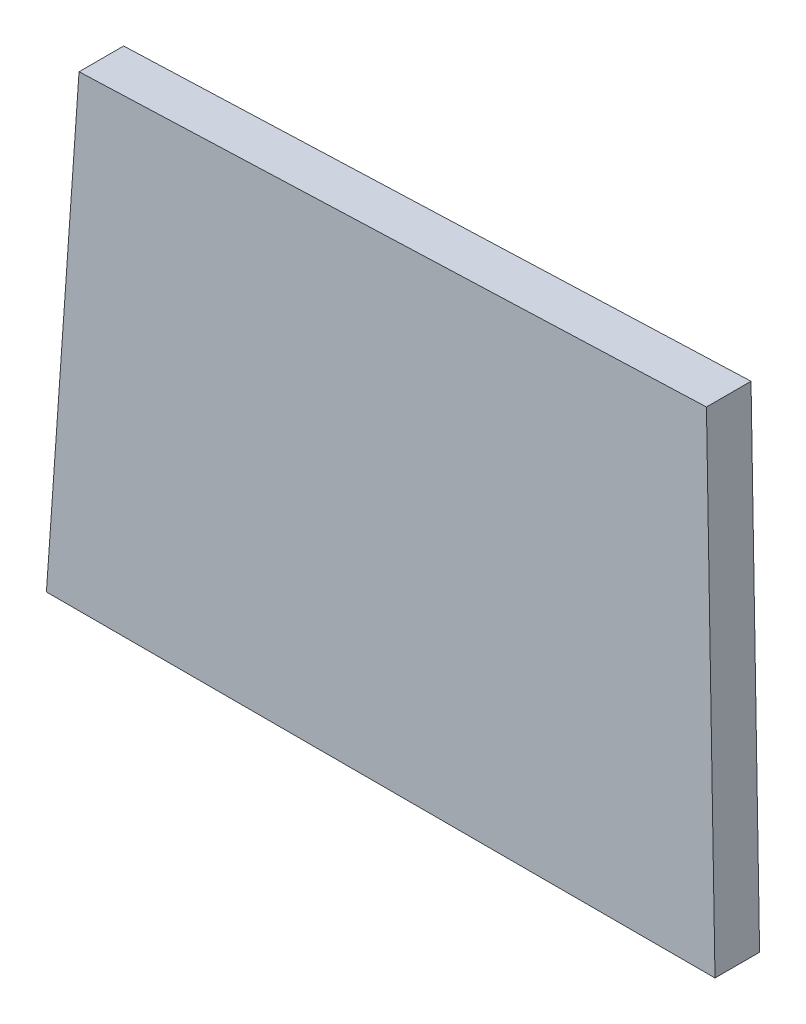
SolidWorks part; units mm, degrees
ref_plane "Ebene vorne" through (0, 0, 0) normal (0, 0, 1) x (1, 0, 0)
ref_plane "Ebene oben" through (0, 0, 0) normal (0, 1, 0) x (1, 0, 0)
ref_plane "Ebene rechts" through (0, 0, 0) normal (1, 0, 0) x (0, 0, -1)
sketch "Skizze1" plane through (0, 0, 0) normal (0, 0, 1) x (1, 0, 0)
  line L0 (0, 0) -> (1.4649, 20.9488)
  line L1 (1.4649, 20.9488) -> (29.616, 21.9966)
  line L2 (29.616, 21.9966) -> (30, 0)
  line L3 (30, 0) -> (0, 0)
  dimension "D1" = 30
  dimension "D2" = 22
  dimension "D3" = 21
  dimension "D4" = 86
  dimension "D5" = 89
extrude "Aufsatz-Linear austragen1" add sketch "Skizze1" along normal blind 2
sketch "Skizze2" plane through (0, 0, 2) normal (0, 0, 1) x (1, 0, 0)
  circle A0 centre (15.9895, 9.4075) radius 18.5517
sketch "Skizze3" plane through (0, 0, 2) normal (0, 0, 1) x (1, 0, 0)
  line L0 (1.5405, 1.9983) -> (29.5405, 1.9983)
  line L1 (1.5405, 1.9983) -> (1.5405, 19.9983)
  line L2 (29.5405, 1.9983) -> (29.5405, 19.9983)
  line L3 (1.5405, 19.9983) -> (29.5405, 19.9983)
  line L4 (1.5405, 1.9983) -> (29.5405, 19.9983) construction
  line L5 (29.5405, 1.9983) -> (1.5405, 19.9983) construction
  line L6 (30, 0) -> (29.616, 21.9966) construction
  line L7 (29.616, 21.9966) -> (1.4649, 20.9488) construction
  point P1 (15.5405, 10.9983)
  point P8 (29.808, 10.9983)
  point P11 (15.5405, 21.4727)
  dimension "D1" = 18
  dimension "D2" = 28
ref_point "SWASI_Vision_Point_1"
ref_point "SWASI_Vision_Point_1_helper"
ref_point "SWASI_Vision_Point_2"
ref_point "SWASI_Vision_Point_2_helper"
ref_point "SWASI_Vision_Point_3"
ref_point "SWASI_Vision_Point_3_helper"
ref_point "SWASI_Vision_Point_4"
ref_plane "SWASI_Alignment_Plane_1" through (0, 0, 0) normal (0, -1, 0) x (-1, 0, 0)
ref_plane "SWASI_Alignment_Plane_2" through (0, 0, 2) normal (0, 0, -1) x (-1, 0, 0)
ref_axis "Achse3" through (0, 0, 2) along (0.9978, 0, -0.0665)
ref_axis "Achse4" through (0, 0, 0) along (0.9978, 0, 0.0665)
ref_point "Surface_Center_Point"
ref_axis "SWASI_Norm_Alignment_Plane_3" through (30, 0, 0) along (-1, 0, 0)
ref_plane "SWASI_Alignment_Plane_3" through (15, 0, 1) normal (-1, 0, 0) x (0, 0, 1)
